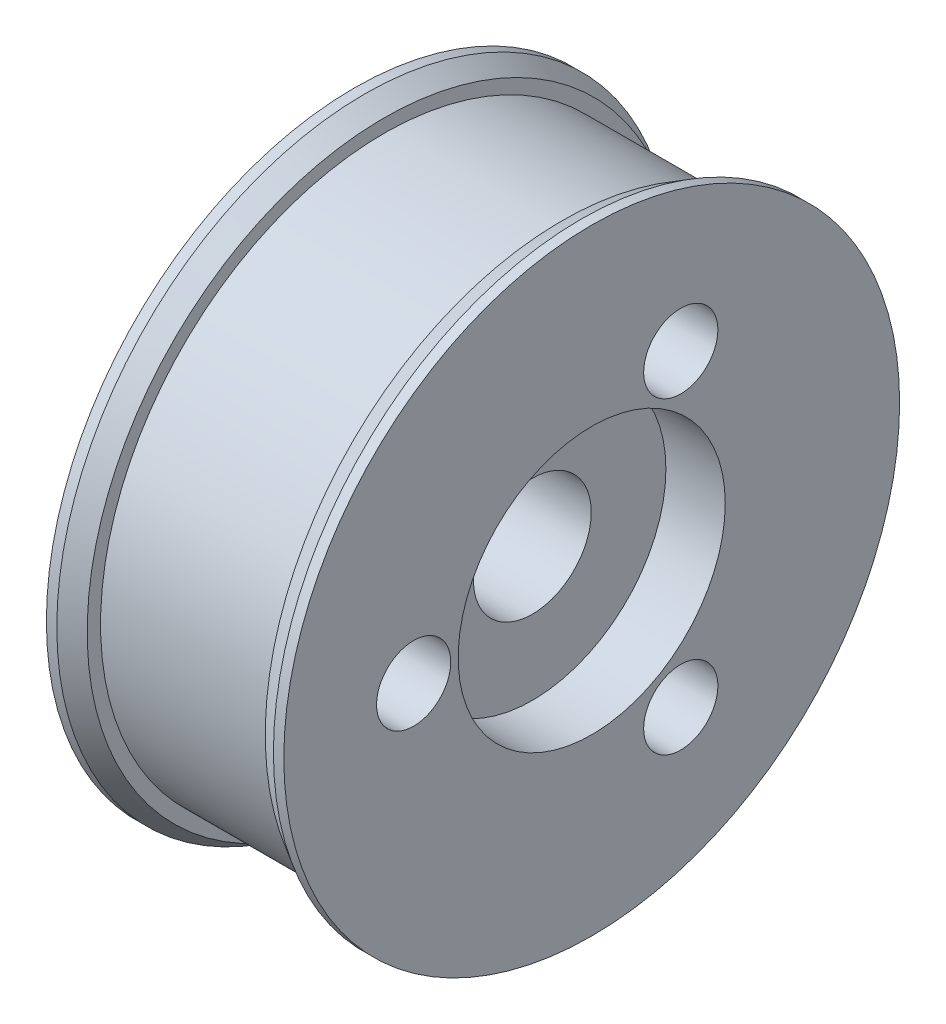
SolidWorks part; units mm, degrees
material "ABS"
ref_plane "Front Plane" through (0, 0, 0) normal (1, 0, 0) x (0, 1, 0)
ref_plane "Top Plane" through (0, 0, 0) normal (0, 0, 1) x (0, 1, 0)
ref_plane "Right Plane" through (0, 0, 0) normal (0, 1, 0) x (-1, 0, 0)
sketch "Sketch1" plane through (0, 0, 0) normal (1, 0, 0) x (0, 1, 0)
  circle A0 centre (0, 0) radius 9.5493
  circle A1 centre (0, 0) radius 8.0761 construction
  circle A2 centre (0, 0) radius 7.4007 construction
  circle A3 centre (0, 0) radius 8.5944 construction
  dimension "D1" = 19.0986
  dimension "D2" = 16.1521
  dimension "D3" = 14.8014
  dimension "D4" = 17.1887
extrude "Boss-Extrude1" add sketch "Sketch1" along normal blind 6
sketch "Sketch4" plane through (0, 0, 0) normal (0, 1, 0) x (-1, 0, 0)
  line L0 (-9.291, 0) -> (5.5255, 0) construction
  line L1 (-6, 0) -> (-6, 10)
  line L2 (-6, 10) -> (-6.6495, 10.375)
  line L3 (-6.6495, 10.375) -> (-7, 10.375)
  line L4 (-7, 10.375) -> (-7, 0)
  line L5 (-7, 0) -> (-6, 0)
  line L6 (0, 0) -> (1, 0)
  line L7 (1, 0) -> (1, 10.375)
  line L8 (1, 10.375) -> (0.6495, 10.375)
  line L9 (0.6495, 10.375) -> (0, 10)
  line L10 (0, 10) -> (0, 0)
  line L11 (-6, 9.5493) -> (-6, -9.5493) construction
  point P11 (0, 0)
  point P15 (-4, 0)
  dimension "D1" = 120
  dimension "D2" = 120
  dimension "D3" = 10
  dimension "D4" = 1
  dimension "D5" = 0.375
revolve "Revolve1" add sketch "Sketch4" angle 360 about L0
sketch "Sketch5" plane through (7, 0, 0) normal (1, 0, 0) x (0, 1, 0)
  circle A0 centre (0, 0) radius 4.5
  circle A1 centre (0, 0) radius 7.5
  dimension "D1" = 9
  dimension "D2" = 15
sketch "Sketch6" plane through (7, 0, 0) normal (1, 0, 0) x (0, 1, 0)
  circle A0 centre (0, 0) radius 1.9844
  dimension "D1" = 3.9688
extrude "Cut-Extrude2" cut sketch "Sketch6" against normal through all
sketch "Sketch7" plane through (-1, 0, 0) normal (-1, 0, 0) x (0, -1, 0)
  line L0 (0, 6) -> (-5.1962, -3) construction
  line L1 (-5.1962, -3) -> (5.1962, -3) construction
  line L2 (5.1962, -3) -> (0, 6) construction
  circle A0 centre (0, 0) radius 6 construction
  point P3 (0, 6)
  point P4 (-5.1962, -3)
  point P5 (5.1962, -3)
  dimension "D1" = 12
hole_wizard "Hole4" positions "Sketch11" profile "Sketch12" legacy end condition through all
sketch "Sketch11" plane through (-1, 0, 0) normal (-1, 0, 0) x (0, 0, 1)
  point P0 (-3, 5.1962)
  point P3 (-3, -5.1962)
  point P6 (6, 0)
sketch "Sketch12" plane through (-1, 5.1962, -3) normal (0, 1, 0) x (0, 0, 1)
  line L0 (0, 0) -> (0, 8)
  line L1 (0, 8) -> (1.25, 8)
  line L2 (1.25, 8) -> (1.25, 1)
  line L3 (1.25, 1) -> (1.75, 1)
  line L4 (1.75, 1) -> (1.75, 0)
  line L5 (1.75, 0) -> (0, 0)
  line L6 (0, 110) -> (0, -10) construction
  dimension "Diameter" = 2.5
  dimension "Depth" = 8
  dimension "C-Bore Diameter" = 3.5
  dimension "C-Bore Depth" = 1
extrude "Cut-Extrude3" cut sketch "Sketch5" against normal blind 2 contours A0 region at (7, 0, 0)
equation "\"DiametralPitch\"= pi / \"Pitch\""
equation "\"NumberTeeth\"= 18"
equation "\"PressureAngle\"= 20"
equation "\"PitchDiameter\"= \"NumberTeeth\" / \"DiametralPitch\""
equation "\"BaseDiameter\"= \"PitchDiameter\" * cos ( \"PressureAngle\" )"
equation "\"Addendum\"= 1 / \"DiametralPitch\""
equation "\"Dedendum\"= 1.25 / \"DiametralPitch\""
equation "\"AddendumDiameter\"= \"PitchDiameter\" + \"Addendum\" + \"Addendum\""
equation "\"DedendumDiameter\"= \"PitchDiameter\" - \"Dedendum\" - \"Dedendum\""
equation "\"D2@Sketch1\"=\"BaseDiameter\""
equation "\"D3@Sketch1\"=\"DedendumDiameter\""
equation "\"D4@Sketch1\"=\"PitchDiameter\""
equation "\"Pitch\"= 3"
equation "\"D1@Sketch6\"=5/32*25.4"
